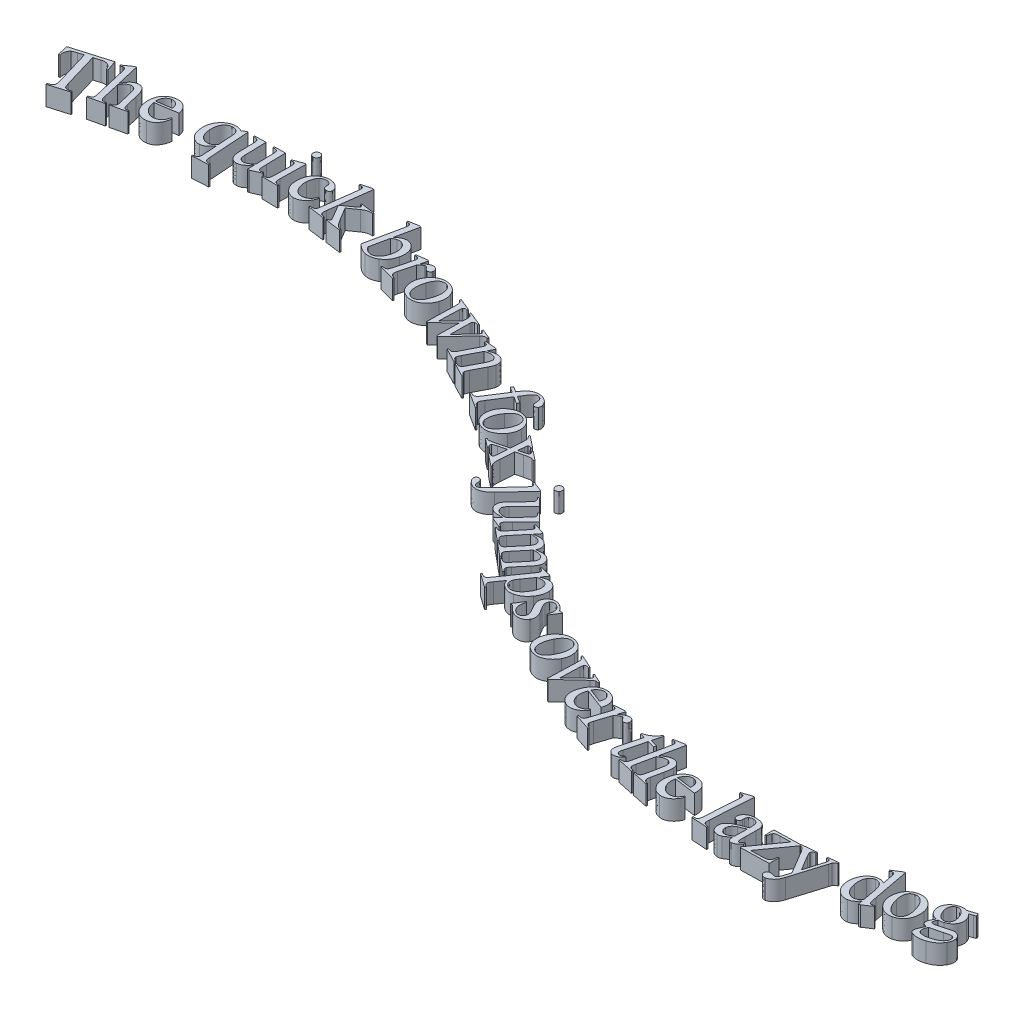
SolidWorks part; units mm, degrees
ref_plane "Front Plane" through (0, 0, 0) normal (0, 0, 1) x (1, 0, 0)
ref_plane "Top Plane" through (0, 0, 0) normal (0, 1, 0) x (1, 0, 0)
ref_plane "Right Plane" through (0, 0, 0) normal (1, 0, 0) x (0, 0, -1)
sketch "Sketch2" plane through (0, 0, 0) normal (0, 1, 0) x (1, 0, 0)
  line L0 (0, 0) -> (50000, 0) construction
  line L1 (0, 0) -> (21.2132, 21.2132) construction
  line L2 (21.2132, 21.2132) -> (63.6396, 21.2132) construction
  arc A0 (21.2132, 21.2132) -> (-21.2132, 21.2132) centre (0, 0) ccw construction
  arc A1 (21.2132, 21.2132) -> (63.6396, 21.2132) centre (42.4264, 42.4264) ccw construction
  text T0 "The quick brown fox jumps over the lazy dog" font "Times New Roman" height in points 10
  dimension "D3" = 90
  dimension "D4" = 30
  dimension "D1" = 30
  dimension "D2" = 45
extrude "Boss-Extrude1" add sketch "Sketch2" along normal blind 1
